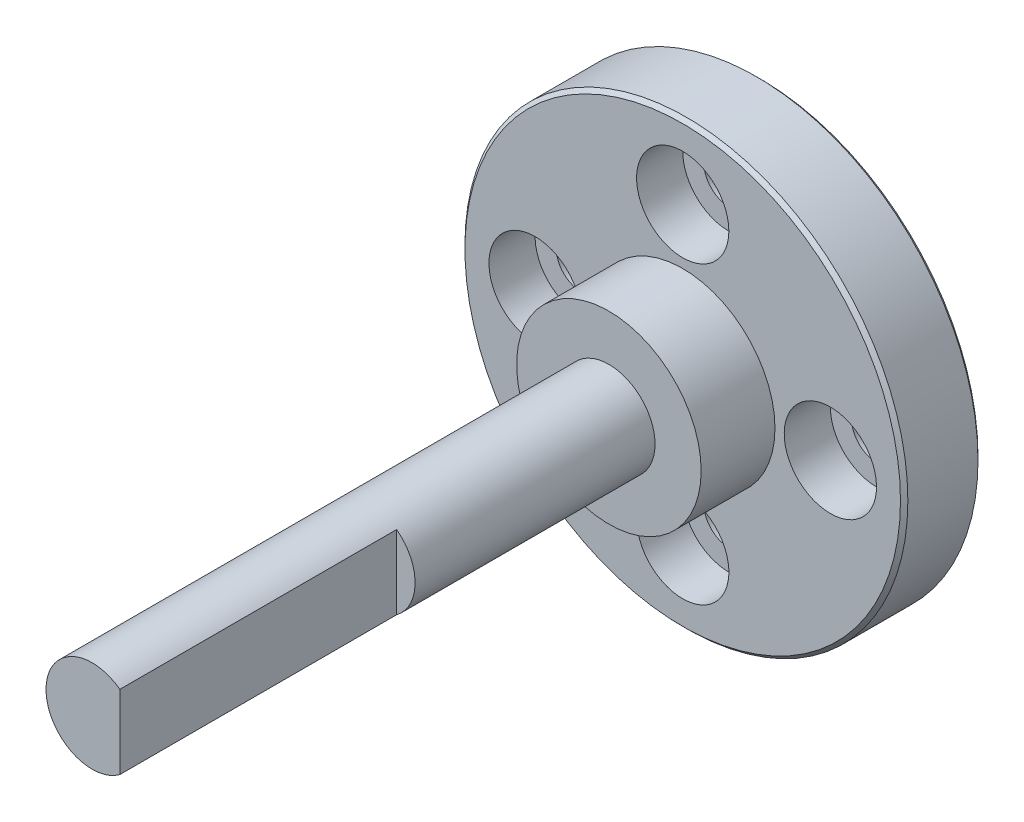
SolidWorks part; units mm, degrees
material "PA(尼龙6)"
ref_plane "前视基准面" through (0, 0, 0) normal (0, 0, 1) x (1, 0, 0)
ref_plane "上视基准面" through (0, 0, 0) normal (0, 1, 0) x (1, 0, 0)
ref_plane "右视基准面" through (0, 0, 0) normal (1, 0, 0) x (0, 0, -1)
sketch "草图1" plane through (0, 0, 0) normal (0, 0, 1) x (1, 0, 0)
  circle A3 centre (0, 0) radius 3
  circle A4 centre (0, 0) radius 12
  point P7 (0, 0)
  dimension "D1" = 24
  dimension "D2" = 6
extrude "凸台-拉伸1" add sketch "草图1" along normal blind 4.2
sketch "草图2" plane through (0, 0, 4.2) normal (0, 0, 1) x (1, 0, 0)
  circle A0 centre (0, 0) radius 5
  point P3 (0, 0)
  dimension "D1" = 10
extrude "凸台-拉伸2" add sketch "草图2" along normal blind 4
hole_wizard "M2.5 六角圆柱头螺钉的柱形沉头孔1" positions "草图8" profile "草图9" counterbore size "M2.5" standard "GB" end condition through all
sketch "草图8" plane through (0, 0, 4.2) normal (0, 0, 1) x (1, 0, 0)
  line L0 (0, 0) -> (0, 8) construction
  point P0 (0, 8)
  dimension "D1" = 8
sketch "草图9" plane through (0, 8, 4.2) normal (1, 0, 0) x (0, -1, 0)
  line L0 (0, 0) -> (0, 4.2)
  line L1 (0, 4.2) -> (1.35, 4.2)
  line L3 (1.35, 4.2) -> (1.35, 2.5)
  line L4 (1.35, 2.5) -> (2.5, 2.5)
  line L5 (2.5, 2.5) -> (2.5, 0)
  line L7 (2.5, 0) -> (0, 0)
  line L11 (0, -6.35) -> (0, 107.95) construction
  dimension "通孔孔直径" = 2.7
  dimension "通孔孔深度" = 4.2
  dimension "柱形沉头孔直径" = 5
  dimension "柱形沉头孔深度" = 2.5
pattern_circular "阵列(圆周)1" count 4 over 360 about axis through (0, 0, 4.2) along (0, 0, -1) of "M2.5 六角圆柱头螺钉的柱形沉头孔1"
sketch "草图10" plane through (0, 0, 4.2) normal (0, 0, -1) x (-1, 0, 0)
  circle A0 centre (0, 0) radius 3 construction
  circle A1 centre (0, 0) radius 3
extrude "凸台-拉伸5" add sketch "草图10" along normal blind 2
chamfer "倒角3" distance 0.2 angle 45 2 edges at (12, 0, 0) (12, 0, 4.2)
sketch "草图12" plane through (0, 0, 8.2) normal (0, 0, 1) x (1, 0, 0)
  circle A0 centre (0, 0) radius 2.5
  dimension "D1" = 5
extrude "凸台-拉伸6" add sketch "草图12" along normal blind 28
sketch "草图13" plane through (0, 0, 36.2) normal (0, 0, 1) x (1, 0, 0)
  line L0 (0, 0) -> (4.1196, 0) construction
  line L1 (1.5, 2.6158) -> (1.5, -2.6158)
  circle A0 centre (0, 0) radius 2.5 construction
  circle A1 centre (0, 0) radius 2.5
  point P6 (1.5, 0)
  circle M2 centre (0, 0) radius 2.5
  dimension "D1" = 1.5
extrude "切除-拉伸1" cut sketch "草图13" against normal blind 15 contours L0 L1 M2 | L1 L0 A1 region at (1.9078, 0.775, 36.2) region at (1.9078, -0.775, 36.2)
